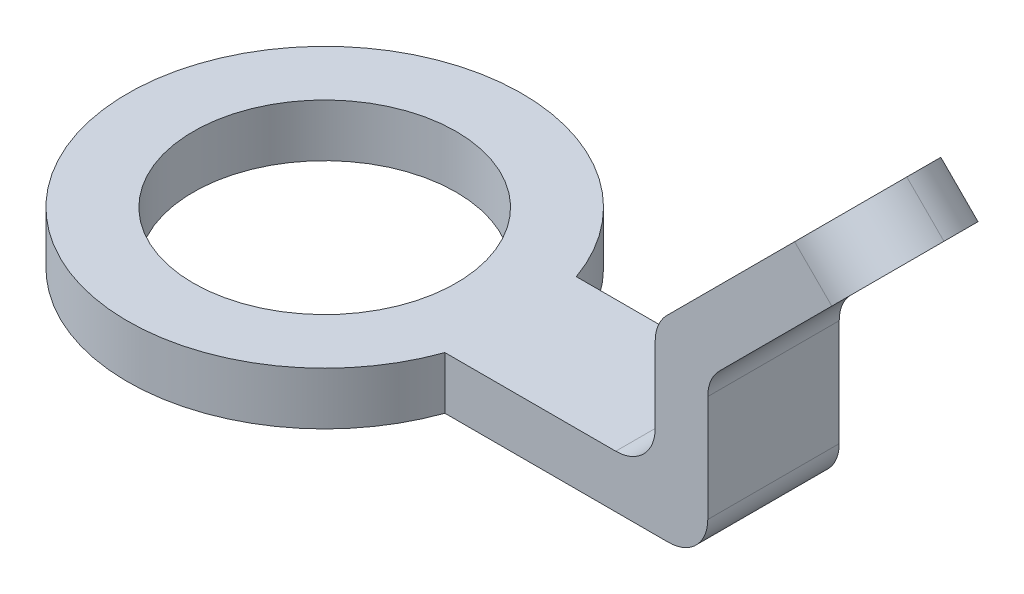
SolidWorks part; units mm, degrees
ref_plane "Front Plane" through (0, 0, 0) normal (0, 0, 1) x (1, 0, 0)
ref_plane "Top Plane" through (0, 0, 0) normal (0, 1, 0) x (1, 0, 0)
ref_plane "Right Plane" through (0, 0, 0) normal (1, 0, 0) x (0, 0, -1)
sketch "Sketch2" plane through (0, 0, 0) normal (0, 1, 0) x (1, 0, 0)
  line L0 (0, 0) -> (34.1421, 0) construction
  line L1 (34.1421, 5) -> (34.1421, -5)
  line L2 (34.1421, -5) -> (14.1421, -5)
  line L3 (34.1421, 5) -> (14.1421, 5)
  arc A0 (14.1421, 5) -> (14.1421, -5) centre (0, 0) ccw
  circle A1 centre (0, 0) radius 10
  dimension "D1" = 30
  dimension "D5" = 20
  dimension "D2" = 5
  dimension "D3" = 5
  dimension "D4" = 20
extrude "Boss-Extrude1" add sketch "Sketch2" along normal blind 4
sketch "Sketch3" plane through (0, 0, 5) normal (0, 0, 1) x (1, 0, 0)
  line L0 (34.1421, 4) -> (34.1421, 12.3431)
  line L1 (34.1421, 12.3431) -> (47.1127, 25.3137)
  line L2 (47.1127, 25.3137) -> (44.2843, 28.1421)
  line L3 (44.2843, 28.1421) -> (30.1421, 14)
  line L4 (30.1421, 14) -> (30.1421, 4)
  line L5 (14.1421, 4) -> (34.1421, 4) construction
  line L6 (30.1421, 4) -> (34.1421, 4)
  dimension "D1" = 4
  dimension "D2" = 4
  dimension "D3" = 135
  dimension "D4" = 10
  dimension "D5" = 20
extrude "Boss-Extrude2" add sketch "Sketch3" against normal blind 10
sketch "Sketch4" plane through (0, 0, 0) normal (0, -1, 0) x (1, 0, 0)
  circle A0 centre (0, 0) radius 12
  circle A1 centre (0, 0) radius 13
  dimension "D1" = 24
  dimension "D2" = 26
extrude "Boss-Extrude3" add sketch "Sketch4" along normal blind 1
fillet "Fillet1" radius 5 2 edges at (45.6985, 26.7279, -5) (45.6985, 26.7279, 5)
sketch "Sketch5" plane through (8.0711, -8.0711, 0) normal (-0.7071, 0.7071, 0) x (0.7071, 0.7071, 0)
  circle A0 centre (46.2132, 0) radius 2.5
  dimension "D1" = 5
hole_wizard "M3 Clearance Hole1" positions "Sketch6" profile "Sketch7" hole size "M3" standard "ANSI Metric" end condition through all
sketch "Sketch6" plane through (8.0711, -8.0711, 0) normal (-0.7071, 0.7071, 0) x (0.7071, 0.7071, 0)
  point P0 (46.2132, 0)
sketch "Sketch7" plane through (40.7487, 24.6066, 0) normal (0, 0, 1) x (-0.7071, -0.7071, 0)
  line L0 (0, 0) -> (0, 22.6066)
  line L1 (0, 22.6066) -> (1.8, 22.6066)
  line L2 (1.8, 22.6066) -> (1.8, 0)
  line L5 (1.8, 0) -> (0, 0)
  line L11 (0, -6.35) -> (0, 107.95) construction
  dimension "Thru Hole Dia." = 3.6
  dimension "Thru Hole Depth" = 22.6066
fillet "Fillet2" radius 3 4 edges at (34.1421, 12.3431, 0) (30.1421, 14, 0) (34.1421, 0, 0) (30.1421, 4, 0)
